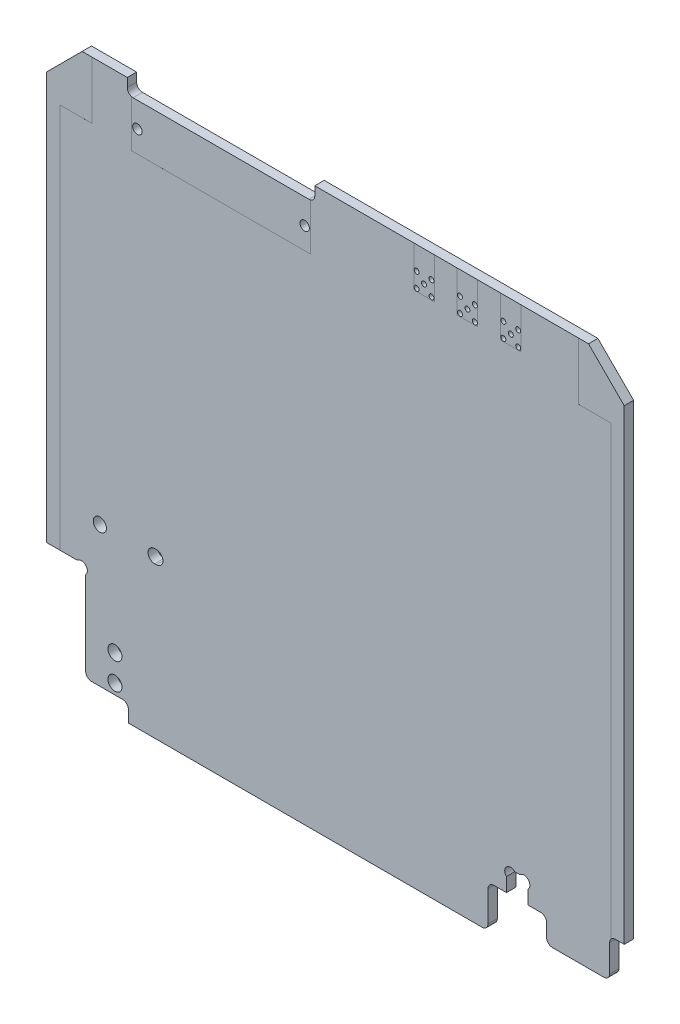
SolidWorks part; units mm, degrees
material "Oshpark board"
ref_plane "Front Plane" through (0, 0, 0) normal (0, 0, 1) x (1, 0, 0)
ref_plane "Top Plane" through (0, 0, 0) normal (0, 1, 0) x (1, 0, 0)
ref_plane "Right Plane" through (0, 0, 0) normal (1, 0, 0) x (0, 0, -1)
ref_plane "Plane4" through (0, 0, -0.0125) normal (0, 0, -1) x (-1, 0, 0)
sketch "Sketch1" plane through (0, 0, -0.0125) normal (0, 0, -1) x (-1, 0, 0)
  line L0 (35.3, -50) -> (35.3, -48)
  line L1 (36.3, -47) -> (45.8, -47)
  line L2 (46.8, -46) -> (46.8, -41.4)
  line L3 (47.8, -40.4) -> (49.3, -40.4)
  line L4 (49.3, -40.4) -> (49.3, 39.2)
  line L5 (49.3, 39.2) -> (43.2, 45.3)
  line L6 (43.2, 45.3) -> (35.5, 45.3)
  line L7 (35.5, 45.3) -> (35.5, 43.8)
  line L8 (34.5, 42.8) -> (4.5, 42.8)
  line L9 (3.5, 43.8) -> (3.5, 45.3)
  line L10 (3.5, 45.3) -> (-43.2, 45.3)
  line L11 (-43.2, 45.3) -> (-49.3, 39.2)
  line L12 (-49.3, 39.2) -> (-49.3, -40.4)
  line L13 (-49.3, -40.4) -> (-47.8, -40.4)
  line L14 (-46.8, -41.4) -> (-46.8, -46)
  line L15 (-45.8, -47) -> (-36.3, -47)
  line L16 (-35.3, -48) -> (-35.3, -50)
  line L17 (-35.3, -50) -> (35.3, -50)
  line L18 (0, -50) -> (0, 45.3) construction
  line L19 (19.5, 42.8) -> (19.5, 25.5258) construction
  line L20 (-13.87, 41.37) -> (-16.41, 38.83) construction
  line L21 (-21.27, 41.37) -> (-23.81, 38.83) construction
  line L22 (-28.67, 41.37) -> (-31.21, 38.83) construction
  arc A0 (35.3, -48) -> (36.3, -47) centre (36.3, -48) cw
  arc A1 (45.8, -47) -> (46.8, -46) centre (45.8, -46) ccw
  arc A2 (46.8, -41.4) -> (47.8, -40.4) centre (47.8, -41.4) cw
  arc A3 (35.5, 43.8) -> (34.5, 42.8) centre (34.5, 43.8) cw
  arc A4 (4.5, 42.8) -> (3.5, 43.8) centre (4.5, 43.8) cw
  arc A5 (-47.8, -40.4) -> (-46.8, -41.4) centre (-47.8, -41.4) cw
  arc A6 (-46.8, -46) -> (-45.8, -47) centre (-45.8, -46) ccw
  arc A7 (-36.3, -47) -> (-35.3, -48) centre (-36.3, -48) cw
  circle A8 centre (-21.27, 41.37) radius 0.425
  circle A9 centre (-23.81, 41.37) radius 0.425
  circle A10 centre (-22.54, 40.1) radius 0.425
  circle A11 centre (-13.87, 41.37) radius 0.425
  circle A12 centre (-23.81, 38.83) radius 0.425
  circle A13 centre (-16.41, 41.37) radius 0.425
  circle A14 centre (-15.14, 40.1) radius 0.425
  circle A15 centre (-21.27, 38.83) radius 0.425
  circle A16 centre (-28.67, 41.37) radius 0.425
  circle A17 centre (-31.21, 41.37) radius 0.425
  circle A18 centre (-16.41, 38.83) radius 0.425
  circle A19 centre (-29.94, 40.1) radius 0.425
  circle A20 centre (-31.21, 38.83) radius 0.425
  circle A21 centre (-28.67, 38.83) radius 0.425
  circle A22 centre (33.775, 38.54) radius 0.8
  circle A23 centre (5.225, 38.54) radius 0.8
  circle A24 centre (-13.87, 38.83) radius 0.425
  point P35 (-15.14, 40.1)
  dimension "D7" = 2.5
  dimension "D8" = 1.6
  dimension "D9" = 14.275
  dimension "D10" = 4.26
  dimension "D11" = 1
  dimension "D12" = 1
  dimension "D13" = 1
  dimension "D14" = 1
  dimension "D15" = 1
  dimension "D16" = 1
  dimension "D17" = 1
  dimension "D18" = 1
  dimension "D26" = 0.85
  dimension "D1" = 98.6
  dimension "D2" = 95.3
  dimension "D3" = 14
  dimension "D4" = 9.6
  dimension "D5" = 2.5
  dimension "D6" = 3
  dimension "D19" = 14
  dimension "D20" = 2.5
  dimension "D21" = 6.1
  dimension "D22" = 6.1
  dimension "D23" = 32
  dimension "D24" = 2.54
  dimension "D25" = 2.54
  dimension "D28" = 7.4
  dimension "D29" = 3.93
  dimension "D30" = 35.43
  dimension "D31" = 45
  dimension "D32" = 45
  dimension "D33" = 29.8
  dimension "D34" = 50
  dimension "D27" = 3
extrude "Boss-Extrude1" add sketch "Sketch1" against normal blind 1.6
sketch "thermalContacts_lower" plane through (0, 0, -0.0125) normal (0, 0, -1) x (-1, 0, 0)
  line L0 (47, 35.5) -> (47, -41.5) construction
  line L1 (41.5, 35.5) -> (41.5, 41.5) construction
  line L2 (41.5, 35.5) -> (47, 35.5) construction
  line L3 (47, 35.5) -> (47, -41.5)
  line L4 (41.5, 35.5) -> (41.5, 41.5)
  line L5 (41.5, 35.5) -> (47, 35.5)
  line L6 (-47, 35.5) -> (-47, -41.5) construction
  line L7 (-41.5, 35.5) -> (-47, 35.5) construction
  line L8 (-41.5, 35.5) -> (-41.5, 41.5) construction
  line L9 (-47, 35.5) -> (-47, -41.5)
  line L10 (-41.5, 35.5) -> (-47, 35.5)
  line L11 (-41.5, 35.5) -> (-41.5, 41.5)
  line L12 (-41.5, 41.5) -> (-41.5, 47) construction
  line L13 (-41.5, 41.5) -> (-49.5, 41.5) construction
  line L14 (-41.5, 41.5) -> (-41.5, 47)
  line L15 (-41.5, 41.5) -> (-49.5, 41.5) construction
  line L16 (41.5, 41.5) -> (41.5, 47) construction
  line L17 (41.5, 41.5) -> (49.5, 41.5) construction
  line L18 (41.5, 41.5) -> (41.5, 47)
  line L19 (41.5, 41.5) -> (49.5, 41.5) construction
  line L20 (47, -41.5) -> (59.8273, -41.5)
  line L21 (59.8273, -41.5) -> (59.8273, 47)
  line L22 (-56.1922, 47) -> (-41.5, 47)
  line L23 (41.5, 47) -> (59.8273, 47)
  line L24 (-56.1922, 47) -> (-56.1922, -41.5)
  line L25 (-47, -41.5) -> (-56.1922, -41.5)
sketch "thermalContacts_upper" plane through (0, 0, 1.5875) normal (0, 0, 1) x (1, 0, 0)
  line L3 (-47, 35.5) -> (-47, -41.5)
  line L4 (-41.5, 35.5) -> (-41.5, 41.5)
  line L5 (-41.5, 35.5) -> (-47, 35.5)
  line L9 (47, 35.5) -> (47, -41.5)
  line L10 (41.5, 35.5) -> (47, 35.5)
  line L11 (41.5, 35.5) -> (41.5, 41.5)
  line L14 (41.5, 41.5) -> (41.5, 47)
  line L15 (41.5, 41.5) -> (49.5, 41.5) construction
  line L18 (-41.5, 41.5) -> (-41.5, 47)
  line L19 (-41.5, 41.5) -> (-49.5, 41.5) construction
  line L20 (47, -41.5) -> (59.8273, -41.5)
  line L21 (59.8273, -41.5) -> (59.8273, 47)
  line L22 (59.8273, 47) -> (41.5, 47)
  line L23 (-41.5, 47) -> (-56.1922, 47)
  line L24 (-56.1922, 47) -> (-56.1922, -41.5)
  line L25 (-56.1922, -41.5) -> (-47, -41.5)
extrude "Cut-Extrude1" cut sketch "thermalContacts_lower" against normal blind 0.0001
extrude "Cut-Extrude2" cut sketch "thermalContacts_upper" against normal blind 0.0001
sketch "partFootprints" plane through (0, 0, 1.5875) normal (0, 0, 1) x (1, 0, 0)
  line L0 (-34.74, 34.84) -> (-34.74, 42.8292)
  line L1 (-4.26, 34.84) -> (-34.74, 34.84)
  line L2 (-41.5, 45.3) -> (-35.5, 45.3) construction
  line L3 (-36.1132, 45.3) -> (-39.5054, 45.3) construction
  line L4 (-4.26, 34.84) -> (-4.26, 42.8292)
  line L5 (-49.3, -40.4) -> (-49.3, 39.2) construction
  line L6 (13.39, 45.3) -> (13.39, 38.35)
  line L7 (13.39, 38.35) -> (16.89, 38.35)
  line L8 (16.89, 38.35) -> (16.89, 45.3)
  line L9 (16.89, 45.3) -> (13.39, 45.3)
  line L10 (20.79, 45.3) -> (20.79, 38.35)
  line L11 (20.79, 38.35) -> (24.29, 38.35)
  line L12 (24.29, 38.35) -> (24.29, 45.3)
  line L13 (24.29, 45.3) -> (20.79, 45.3)
  line L14 (28.19, 45.3) -> (28.19, 38.35)
  line L15 (28.19, 38.35) -> (31.69, 38.35)
  line L16 (31.69, 38.35) -> (31.69, 45.3)
  line L17 (31.69, 45.3) -> (28.19, 45.3)
  line L19 (14.12, 38.35) -> (16.16, 38.35) construction
  line L20 (-34.74, 42.8292) -> (-4.26, 42.8292)
  line L21 (-3.5, 45.3) -> (41.5, 45.3) construction
  line L22 (14.12, 38.35) -> (16.16, 38.35) construction
  line L23 (13.39, 41.85) -> (13.39, 38.35) construction
  line L24 (16.89, 41.85) -> (16.89, 38.35) construction
  line L25 (13.39, 41.85) -> (13.39, 38.35) construction
  line L26 (16.89, 41.85) -> (16.89, 38.35) construction
  arc A0 (-35.5, 43.8) -> (-34.5, 42.8) centre (-34.5, 43.8) ccw construction
  arc A1 (-4.5, 42.8) -> (-3.5, 43.8) centre (-4.5, 43.8) ccw construction
  dimension "D1" = 10.46
  dimension "D2" = 14.56
  dimension "D3" = 30.48
  dimension "D7" = 7.4
  dimension "D6" = 3
extrude "Cut-Extrude3" cut sketch "partFootprints" against normal blind 0.0001
sketch "Sketch2" plane through (0, 0, 1.5875) normal (0, 0, 1) x (1, 0, 0)
  line L0 (35.1, -50) -> (35.1, -37.5518) construction
  line L1 (35.3, -50) -> (-35.3, -50) construction
  line L2 (27, -50) -> (27, -36.9095) construction
  line L3 (35.3, -48) -> (35.3, -50) construction
  line L4 (29.2, -42.8) -> (29.2, -40.4142)
  line L5 (27, -39) -> (35.1, -39) construction
  line L6 (30.6142, -39) -> (31.4858, -39)
  line L7 (32.9, -40.4142) -> (32.9, -42.8)
  line L8 (26.05, -50) -> (36.05, -50)
  line L9 (30.6142, -39) -> (31.4858, -39) construction
  line L10 (26.05, -50) -> (26.05, -42.8)
  line L11 (26.05, -42.8) -> (29.2, -42.8)
  line L12 (31.05, -39) -> (31.05, -50) construction
  line L13 (36.05, -42.8) -> (32.9, -42.8)
  line L14 (36.05, -50) -> (36.05, -42.8)
  line L15 (48.0683, 27.2) -> (36.7758, 27.2) construction
  line L16 (48.0683, 35.5) -> (35.6387, 35.5) construction
  line L17 (42.1, 29.55) -> (39.0071, 29.55) construction
  line L18 (38.3, 35.5) -> (38.3, 27.2) construction
  line L19 (38.3, 30.2571) -> (38.3, 32.4429) construction
  line L20 (39.0071, 33.15) -> (42.1, 33.15) construction
  line L21 (49.3, 29.1) -> (49.3, 33.6) construction
  line L22 (38.3, 30.2571) -> (38.3, 32.4429) construction
  line L23 (49.3, 29.1) -> (42.1, 29.1) construction
  line L24 (42.1, 29.1) -> (42.1, 29.55) construction
  line L25 (38.3, 31.35) -> (49.3, 31.35) construction
  line L26 (42.1, 33.6) -> (42.1, 33.15) construction
  line L27 (49.3, 33.6) -> (42.1, 33.6) construction
  line L28 (49.3, -40.4) -> (49.3, 39.2) construction
  line L30 (31.69, 45.3) -> (41.5, 45.3) construction
  arc A0 (29.2, -40.4142) -> (30.6142, -39) centre (29.9071, -39.7071) cw
  arc A1 (31.4858, -39) -> (32.9, -40.4142) centre (32.1929, -39.7071) cw
  arc A2 (39.0071, 29.55) -> (38.3, 30.2571) centre (38.6536, 29.9036) cw construction
  arc A3 (38.3, 32.4429) -> (39.0071, 33.15) centre (38.6536, 32.7964) cw construction
  point P8 (35.3, -49)
  point P39 (38.3, 31.35)
  point P46 (38.3, 31.35)
  point P47 (38.3, 29.55)
  point P48 (38.3, 33.15)
  point P57 (31.05, -39)
  point P59 (32.9, -39)
  point P60 (29.2, -39)
  dimension "D5" = 1
  dimension "D8" = 0.5
  dimension "D1" = 0.2
  dimension "D2" = 8.3
  dimension "D3" = 3.7
  dimension "D4" = 11
  dimension "D6" = 3.8
  dimension "D7" = 10
  dimension "D9" = 3.6
  dimension "D10" = 11
  dimension "D11" = 3.8
  dimension "D12" = 4.5
  dimension "D13" = 9.8
  dimension "D14" = 8.3
extrude "Cut-Extrude4" cut sketch "Sketch2" against normal through all
sketch "Sketch3" plane through (0, 0, 1.5875) normal (0, 0, 1) x (1, 0, 0)
  line L0 (45.8, -47) -> (36.3, -47) construction
  line L1 (31.741, -47) -> (39.5208, -47)
  line L2 (31.741, -47) -> (31.741, -52.1552)
  line L3 (31.741, -52.1552) -> (39.5208, -52.1552)
  line L4 (39.5208, -47) -> (39.5208, -52.1552)
extrude "Cut-Extrude5" cut sketch "Sketch3" against normal blind 10
fillet "Fillet1" radius 1 4 edges at (36.05, -42.8, 0.7875) (26.05, -42.8, 0.7875) (36.05, -47, 0.7875) (26.05, -50, 0.7875)
sketch "Sketch4" plane through (0, 0, 1.5875) normal (0, 0, 1) x (1, 0, 0)
  line L0 (-36.3, -47) -> (-45.8, -47) construction
  line L1 (-51.3808, -30.3) -> (-44.0142, -30.3)
  line L2 (-51.3808, -30.3) -> (-51.3808, -47)
  line L3 (-51.3808, -47) -> (-42.6, -47)
  line L4 (-42.6, -31.7142) -> (-42.6, -47)
  line L5 (-42.8, -37.156) -> (-42.8, -48.7489) construction
  line L6 (-44.0142, -30.3) -> (-42.6, -30.3) construction
  line L7 (-42.6, -30.3) -> (-42.6, -31.7142) construction
  arc A0 (-44.0142, -30.3) -> (-42.6, -31.7142) centre (-43.3071, -31.0071) cw
  point P11 (-42.6, -30.3)
  dimension "D1" = 1
  dimension "D2" = 0.2
  dimension "D3" = 16.7
extrude "Cut-Extrude6" cut sketch "Sketch4" against normal through all
fillet "Fillet2" radius 1 1 edges at (-42.6, -47, 0.7875)
sketch "Sketch5" plane through (0, 0, 1.5875) normal (0, 0, 1) x (1, 0, 0)
  line L0 (-30.525, -24.225) -> (-30.825, -24.225) construction
  line L1 (-30.525, -24.225) -> (-30.825, -24.225)
  line L2 (-30.825, -21.975) -> (-30.525, -21.975) construction
  line L3 (-30.825, -21.975) -> (-30.525, -21.975)
  circle A0 centre (-40.175, -23.1) radius 1.125 construction
  circle A1 centre (-40.175, -23.1) radius 1.125
  arc A2 (-30.825, -21.975) -> (-30.825, -24.225) centre (-30.825, -23.1) ccw construction
  arc A3 (-30.525, -24.225) -> (-30.525, -21.975) centre (-30.525, -23.1) ccw construction
  arc A4 (-30.825, -21.975) -> (-30.825, -24.225) centre (-30.825, -23.1) ccw
  arc A5 (-30.525, -24.225) -> (-30.525, -21.975) centre (-30.525, -23.1) ccw
extrude "Cut-Extrude7" cut sketch "Sketch5" against normal through all
sketch "Sketch6" plane through (0, 0, 1.5875) normal (0, 0, 1) x (1, 0, 0)
  circle A1 centre (-37.6, -40.75) radius 1.2
  circle A2 centre (-37.6, -45.25) radius 1.2 construction
  circle A3 centre (-37.6, -45.25) radius 1.2
  circle A4 centre (-37.6, -40.75) radius 1.2 construction
extrude "Cut-Extrude8" cut sketch "Sketch6" against normal through all
